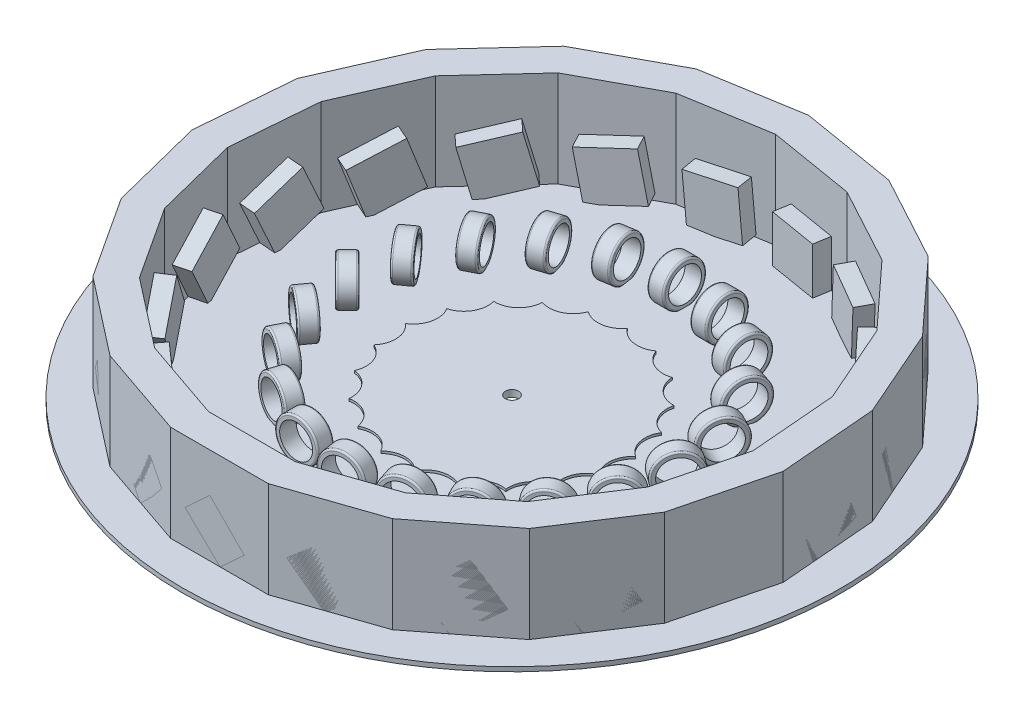
SolidWorks part; units mm, degrees
ref_plane "Front Plane" through (0, 0, 0) normal (0, 0, 1) x (1, 0, 0)
ref_plane "Top Plane" through (0, 0, 0) normal (0, 1, 0) x (1, 0, 0)
ref_plane "Right Plane" through (0, 0, 0) normal (1, 0, 0) x (0, 0, -1)
sketch "Sketch1" plane through (0, 0, 0) normal (0, 1, 0) x (1, 0, 0)
  circle A0 centre (0, 0) radius 100
  circle A1 centre (0, 0) radius 2
  dimension "D1" = 200
  dimension "D2" = 4
extrude "Base Platter" add sketch "Sketch1" along normal blind 0.75
sketch "Sketch2" plane through (0, 0.75, 0) normal (0, 1, 0) x (1, 0, 0)
  line L0 (0, 0) -> (0, 35) construction
  line L1 (0, 0) -> (10.3164, 33.445) construction
  line L2 (0, 0) -> (19.7162, 28.9184) construction
  line L3 (0, 0) -> (27.3641, 21.8221) construction
  line L4 (0, 0) -> (32.5806, 12.7869) construction
  line L5 (0, 0) -> (34.9021, 2.6156) construction
  line L6 (0, 0) -> (34.1225, -7.7882) construction
  line L7 (0, 0) -> (30.3109, -17.5) construction
  line L8 (0, 0) -> (23.806, -25.6568) construction
  line L9 (0, 0) -> (15.1859, -31.5339) construction
  line L10 (0, 0) -> (5.2165, -34.6091) construction
  line L11 (0, 0) -> (-5.2165, -34.6091) construction
  line L12 (0, 0) -> (-15.1859, -31.5339) construction
  line L13 (0, 0) -> (-23.806, -25.6568) construction
  line L14 (0, 0) -> (-30.3109, -17.5) construction
  line L15 (0, 0) -> (-34.1225, -7.7882) construction
  line L16 (0, 0) -> (-34.9021, 2.6156) construction
  line L17 (0, 0) -> (-32.5806, 12.7869) construction
  line L18 (0, 0) -> (-27.3641, 21.8221) construction
  line L19 (0, 0) -> (-19.7162, 28.9184) construction
  line L20 (0, 0) -> (-10.3164, 33.445) construction
  line L21 (0, 0) -> (4.4705, 29.665) construction
  line L22 (0, 0) -> (13.0158, 27.0294) construction
  line L23 (0, 0) -> (20.4046, 21.9921) construction
  line L24 (0, 0) -> (25.9804, 15.0006) construction
  line L25 (0, 0) -> (29.2477, 6.6764) construction
  line L26 (0, 0) -> (29.9162, -2.2412) construction
  line L27 (0, 0) -> (27.9265, -10.9595) construction
  line L28 (0, 0) -> (23.4554, -18.7041) construction
  line L29 (0, 0) -> (16.9002, -24.7867) construction
  line L30 (0, 0) -> (8.8434, -28.667) construction
  line L31 (0, 0) -> (0.0007, -30) construction
  line L32 (0, 0) -> (-8.8419, -28.6674) construction
  line L33 (0, 0) -> (-16.899, -24.7876) construction
  line L34 (0, 0) -> (-23.4545, -18.7053) construction
  line L35 (0, 0) -> (-27.9259, -10.9609) construction
  line L36 (0, 0) -> (-29.9161, -2.2426) construction
  line L37 (0, 0) -> (-29.248, 6.6749) construction
  line L38 (0, 0) -> (-25.9811, 14.9994) construction
  line L39 (0, 0) -> (-20.4057, 21.991) construction
  line L40 (0, 0) -> (-13.0172, 27.0287) construction
  line L41 (0, 0) -> (-4.472, 29.6648) construction
  circle A0 centre (0, 0) radius 30 construction
  circle A1 centre (0, 0) radius 2 construction
  circle A2 centre (0, 0) radius 35 construction
  arc A3 (-19.7162, 28.9184) -> (-10.3164, 33.445) centre (-17.2797, 35.8816) ccw
  arc A4 (-10.3164, 33.445) -> (0, 35) centre (-5.9357, 39.3807) ccw
  arc A5 (0, 35) -> (10.3164, 33.445) centre (5.9357, 39.3807) ccw
  arc A6 (10.3164, 33.445) -> (19.7162, 28.9184) centre (17.2797, 35.8816) ccw
  arc A7 (19.7162, 28.9184) -> (27.3641, 21.8221) centre (27.0883, 29.1942) ccw
  arc A8 (27.3641, 21.8221) -> (32.5806, 12.7869) centre (34.4899, 19.9128) ccw
  arc A9 (32.5806, 12.7869) -> (34.9021, 2.6156) centre (38.827, 8.862) ccw
  arc A10 (34.9021, 2.6156) -> (34.1225, -7.7882) centre (39.7142, -2.9762) ccw
  arc A11 (34.1225, -7.7882) -> (30.3109, -17.5) centre (37.0726, -14.5499) ccw
  arc A12 (30.3109, -17.5) -> (23.806, -25.6568) centre (31.1369, -24.8308) ccw
  arc A13 (23.806, -25.6568) -> (15.1859, -31.5339) centre (22.4345, -32.9054) ccw
  arc A14 (15.1859, -31.5339) -> (5.2165, -34.6091) centre (11.7388, -38.0562) ccw
  arc A15 (5.2165, -34.6091) -> (-5.2165, -34.6091) centre (0, -39.8256) ccw
  arc A16 (-5.2165, -34.6091) -> (-15.1859, -31.5339) centre (-11.7388, -38.0562) ccw
  arc A17 (-15.1859, -31.5339) -> (-23.806, -25.6568) centre (-22.4345, -32.9054) ccw
  arc A18 (-23.806, -25.6568) -> (-30.3109, -17.5) centre (-31.1369, -24.8308) ccw
  arc A19 (-30.3109, -17.5) -> (-34.1225, -7.7882) centre (-37.0726, -14.5499) ccw
  arc A20 (-34.1225, -7.7882) -> (-34.9021, 2.6156) centre (-39.7142, -2.9762) ccw
  arc A21 (-34.9021, 2.6156) -> (-32.5806, 12.7869) centre (-38.827, 8.862) ccw
  arc A22 (-32.5806, 12.7869) -> (-27.3641, 21.8221) centre (-34.4899, 19.9128) ccw
  arc A23 (-27.3641, 21.8221) -> (-19.7162, 28.9184) centre (-27.0883, 29.1942) ccw
  circle A24 centre (0, 0) radius 2
  point P28 (0, 0)
  point P50 (0, 0)
  point P112 (0, 0)
  dimension "D1" = 60
  dimension "D2" = 70
  dimension "D7" = 4
  dimension "D4" = 8.57
  dimension "D3" = 21
  dimension "D5" = 21
  dimension "D6" = 21
extrude "Inner Design" add sketch "Sketch2" along normal blind 1.3
sketch "Sketch3" plane through (0, 0.75, 0) normal (0, 1, 0) x (1, 0, 0)
  line L1 (0, 90) -> (-29.223, 85.1236)
  line L2 (-29.223, 85.1236) -> (-55.2791, 71.0226)
  line L3 (-55.2791, 71.0226) -> (-75.345, 49.2253)
  line L4 (-75.345, 49.2253) -> (-87.246, 22.0937)
  line L5 (-87.246, 22.0937) -> (-89.6926, -7.4321)
  line L6 (-89.6926, -7.4321) -> (-82.4196, -36.1526)
  line L7 (-82.4196, -36.1526) -> (-66.2152, -60.9553)
  line L8 (-66.2152, -60.9553) -> (-42.8353, -79.1526)
  line L9 (-42.8353, -79.1526) -> (-14.8135, -88.7725)
  line L10 (-14.8135, -88.7725) -> (14.8135, -88.7725)
  line L11 (14.8135, -88.7725) -> (42.8353, -79.1526)
  line L12 (42.8353, -79.1526) -> (66.2152, -60.9553)
  line L13 (66.2152, -60.9553) -> (82.4196, -36.1526)
  line L14 (82.4196, -36.1526) -> (89.6926, -7.4321)
  line L15 (89.6926, -7.4321) -> (87.246, 22.0937)
  line L16 (87.246, 22.0937) -> (75.345, 49.2253)
  line L17 (75.345, 49.2253) -> (55.2791, 71.0226)
  line L18 (55.2791, 71.0226) -> (29.223, 85.1236)
  line L19 (29.223, 85.1236) -> (0, 90)
  line L20 (0, 80) -> (-25.976, 75.6654)
  line L21 (-25.976, 75.6654) -> (-49.137, 63.1312)
  line L22 (-49.137, 63.1312) -> (-66.9733, 43.7559)
  line L23 (-66.9733, 43.7559) -> (-77.552, 19.6388)
  line L24 (-77.552, 19.6388) -> (-79.7268, -6.6063)
  line L25 (-79.7268, -6.6063) -> (-73.2619, -32.1356)
  line L26 (-73.2619, -32.1356) -> (-58.8579, -54.1825)
  line L27 (-58.8579, -54.1825) -> (-38.0758, -70.3579)
  line L28 (-38.0758, -70.3579) -> (-13.1676, -78.9089)
  line L29 (-13.1676, -78.9089) -> (13.1676, -78.9089)
  line L30 (13.1676, -78.9089) -> (38.0758, -70.3579)
  line L31 (38.0758, -70.3579) -> (58.8579, -54.1825)
  line L32 (58.8579, -54.1825) -> (73.2619, -32.1356)
  line L33 (73.2619, -32.1356) -> (79.7268, -6.6063)
  line L34 (79.7268, -6.6063) -> (77.552, 19.6388)
  line L35 (77.552, 19.6388) -> (66.9733, 43.7559)
  line L36 (66.9733, 43.7559) -> (49.137, 63.1312)
  line L37 (49.137, 63.1312) -> (25.976, 75.6654)
  line L38 (25.976, 75.6654) -> (0, 80)
  circle A0 centre (0, 0) radius 90 construction
  circle A1 centre (0, 0) radius 80 construction
  circle A2 centre (0, 0) radius 88.7725 construction
  circle A3 centre (0, 0) radius 78.9089 construction
  dimension "D1" = 180
  dimension "D2" = 160
extrude "Cube Face Reference" add sketch "Sketch3" along normal blind 29.8 separate body
sketch "Sketch4" plane through (14.6115, 0, -87.5618) normal (0.1646, 0, -0.9864) x (-0.9864, 0, -0.1646)
  line L0 (0, 0.75) -> (0, 30.55) construction
  line L1 (100, 0.75) -> (-100, 0.75) construction
  line L2 (-14.8135, 30.55) -> (14.8135, 30.55) construction
  line L3 (-14.8135, 0.75) -> (14.8135, 0.75) construction
  line L4 (-7.4075, 0.75) -> (7.4075, 0.75)
  line L5 (-7.4075, 0.75) -> (-7.4075, 15.57)
  line L6 (-7.4075, 15.57) -> (7.4075, 15.57)
  line L7 (7.4075, 0.75) -> (7.4075, 15.57)
  point P12 (0, 15.57)
  dimension "D1" = 14.815
  dimension "D2" = 14.82
extrude "First Cube" add sketch "Sketch4" against normal blind 14.82 separate body
sketch "Sketch5" plane through (42.251, 0, -78.0731) normal (0.4759, 0, -0.8795) x (-0.8795, 0, -0.4759)
  line L0 (-6.7728, 0.75) -> (7.9966, 1.9738)
  line L1 (-14.8135, 0.75) -> (14.8135, 0.75) construction
  line L2 (7.9966, 1.9738) -> (6.7728, 16.7432)
  line L3 (6.7728, 16.7432) -> (-7.9966, 15.5194)
  line L4 (-7.9966, 15.5194) -> (-6.7728, 0.75)
  line L5 (6.7728, 16.7432) -> (-6.7728, 0.75) construction
  line L6 (7.9966, 1.9738) -> (-7.9966, 15.5194) construction
  line L7 (100, 0.75) -> (-100, 0.75) construction
  line L8 (-14.8135, 30.55) -> (14.8135, 30.55) construction
  point P4 (0, 0)
  point P11 (0, 30.55)
  point P12 (0, 8.7466)
  dimension "D1" = 14.82
  dimension "D2" = 14.82
  dimension "D3" = 4.737
extrude "Boss-Extrude6" add sketch "Sketch5" against normal blind 14.82 separate body
sketch "Sketch6" plane through (65.3121, 0, -60.124) normal (0.7357, 0, -0.6773) x (-0.6773, 0, -0.7357)
  line L0 (-6.0893, 0.75) -> (-8.5286, 15.3679)
  line L1 (-14.8135, 0.75) -> (14.8135, 0.75) construction
  line L2 (-8.5286, 15.3679) -> (6.0893, 17.8072)
  line L3 (6.0893, 17.8072) -> (8.5286, 3.1893)
  line L4 (8.5286, 3.1893) -> (-6.0893, 0.75)
  line L5 (6.0893, 17.8072) -> (-6.0893, 0.75) construction
  line L6 (-8.5286, 15.3679) -> (8.5286, 3.1893) construction
  point P4 (0, 9.2786)
  dimension "D1" = 14.82
  dimension "D2" = 14.82
  dimension "D3" = 9.474
extrude "Boss-Extrude7" add sketch "Sketch6" against normal blind 14.82 separate body
sketch "Sketch7" plane through (81.2955, 0, -35.6595) normal (0.9158, 0, -0.4017) x (-0.4017, 0, -0.9158)
  line L0 (-5.3642, 0.75) -> (-9.0023, 15.1165)
  line L2 (-9.0023, 15.1165) -> (5.3642, 18.7546)
  line L3 (5.3642, 18.7546) -> (9.0023, 4.3881)
  line L4 (9.0023, 4.3881) -> (-5.3642, 0.75)
  line L5 (5.3642, 18.7546) -> (-5.3642, 0.75) construction
  line L6 (9.0023, 4.3881) -> (-9.0023, 15.1165) construction
  line L7 (100, 0.75) -> (-100, 0.75) construction
  line L8 (-14.8135, 0.75) -> (14.8135, 0.75) construction
  point P2 (0, 0)
  point P4 (0, 9.7523)
  dimension "D1" = 14.82
  dimension "D2" = 14.82
  dimension "D3" = 14.211
extrude "Boss-Extrude9" add sketch "Sketch7" against normal blind 14.82 separate body
sketch "Sketch8" plane through (88.4693, 0, -7.3308) normal (0.9966, 0, -0.0826) x (-0.0826, 0, -0.9966)
  line L0 (-4.6025, 0.75) -> (-9.4145, 14.767)
  line L2 (-9.4145, 14.767) -> (4.6025, 19.5791)
  line L3 (4.6025, 19.5791) -> (9.4145, 5.562)
  line L4 (9.4145, 5.562) -> (-4.6025, 0.75)
  line L5 (-14.8135, 0.75) -> (14.8135, 0.75) construction
  line L6 (-4.6025, 0.75) -> (4.6025, 19.5791) construction
  line L7 (9.4145, 5.562) -> (-9.4145, 14.767) construction
  line L8 (-14.8135, 30.55) -> (14.8135, 30.55) construction
  point P8 (0, 30.55)
  point P9 (0, 10.1645)
  dimension "D1" = 14.82
  dimension "D2" = 14.82
  dimension "D3" = 18.947
extrude "Boss-Extrude10" add sketch "Sketch8" against normal blind 14.82 separate body
sketch "Sketch9" plane through (86.0561, 0, 21.7924) normal (0.9694, 0, 0.2455) x (0.2455, 0, -0.9694)
  line L0 (-3.8093, 0.75) -> (-9.7624, 14.3218)
  line L1 (-14.8135, 0.75) -> (14.8135, 0.75) construction
  line L2 (-9.7624, 14.3218) -> (3.8093, 20.2749)
  line L3 (3.8093, 20.2749) -> (9.7624, 6.7031)
  line L4 (9.7624, 6.7031) -> (-3.8093, 0.75)
  line L5 (-3.8093, 0.75) -> (3.8093, 20.2749)
  line L6 (9.7624, 6.7031) -> (-9.7624, 14.3218)
  point P4 (0, 10.5124)
  dimension "D1" = 14.82
  dimension "D2" = 14.82
  dimension "D3" = 23.684
extrude "Boss-Extrude11" add sketch "Sketch9" against normal blind 14.82 separate body contours L6 L5 L2 | L6 L3 L5 | L4 L6 L5 | L5 L6 L0 region at (86.5432, 5.9885, 19.8687) region at (84.9455, 8.5281, 26.1779) region at (85.569, 15.0364, 23.716) region at (87.1667, 12.4968, 17.4069)
sketch "Sketch10" plane through (74.3174, 0, 48.554) normal (0.8372, 0, 0.5469) x (0.5469, 0, -0.8372)
  line L0 (-2.9901, 0.75) -> (-10.0437, 13.7838)
  line L1 (-14.8135, 0.75) -> (14.8135, 0.75) construction
  line L2 (-10.0437, 13.7838) -> (2.9901, 20.8373)
  line L3 (2.9901, 20.8373) -> (10.0437, 7.8035)
  line L4 (10.0437, 7.8035) -> (-2.9901, 0.75)
  line L5 (-2.9901, 0.75) -> (2.9901, 20.8373) construction
  line L6 (10.0437, 7.8035) -> (-10.0437, 13.7838) construction
  point P4 (0, 0.75)
  point P7 (0, 10.7937)
  dimension "D1" = 14.82
  dimension "D2" = 14.82
  dimension "D3" = 28.421
extrude "Boss-Extrude12" add sketch "Sketch10" against normal blind 14.82 separate body
sketch "Sketch11" plane through (54.5252, 0, 70.054) normal (0.6142, 0, 0.7891) x (0.7891, 0, -0.6142)
  line L0 (-2.1505, 0.75) -> (-10.2563, 13.1568)
  line L1 (-14.8135, 0.75) -> (14.8135, 0.75) construction
  line L2 (-10.2563, 13.1568) -> (2.1505, 21.2626)
  line L3 (2.1505, 21.2626) -> (10.2563, 8.8558)
  line L4 (10.2563, 8.8558) -> (-2.1505, 0.75)
  line L5 (2.1505, 21.2626) -> (-2.1505, 0.75) construction
  line L6 (10.2563, 8.8558) -> (-10.2563, 13.1568) construction
  line L7 (-14.8135, 30.55) -> (14.8135, 30.55) construction
  line L8 (100, 0.75) -> (-100, 0.75) construction
  point P8 (0, 30.55)
  point P9 (0, 11.0063)
  dimension "D1" = 14.82
  dimension "D2" = 14.82
  dimension "D3" = 33.158
extrude "Boss-Extrude14" add sketch "Sketch11" against normal blind 14.82 separate body
sketch "Sketch12" plane through (28.8244, 0, 83.9626) normal (0.3247, 0, 0.9458) x (0.9458, 0, -0.3247)
  line L0 (-1.2962, 0.75) -> (-10.3988, 12.4451)
  line L1 (100, 0.75) -> (-100, 0.75) construction
  line L2 (-10.3988, 12.4451) -> (1.2962, 21.5477)
  line L3 (1.2962, 21.5477) -> (10.3988, 9.8526)
  line L4 (10.3988, 9.8526) -> (-1.2962, 0.75)
  line L5 (1.2962, 21.5477) -> (-1.2962, 0.75) construction
  line L6 (-10.3988, 12.4451) -> (10.3988, 9.8526) construction
  line L7 (-14.8135, 30.55) -> (14.8135, 30.55) construction
  line L8 (-14.8135, 0.75) -> (14.8135, 0.75) construction
  point P8 (0, 30.55)
  point P9 (0, 11.1488)
  dimension "D1" = 14.82
  dimension "D2" = 14.82
  dimension "D3" = 37.895
extrude "Boss-Extrude15" add sketch "Sketch12" against normal blind 14.82 separate body
sketch "Sketch13" plane through (0, 0, 88.7725) normal (0, 0, 1) x (1, 0, 0)
  line L0 (-0.4331, 0.75) -> (-10.4704, 11.6534)
  line L1 (-14.8135, 0.75) -> (14.8135, 0.75) construction
  line L2 (-10.4704, 11.6534) -> (0.4331, 21.6907)
  line L3 (0.4331, 21.6907) -> (10.4704, 10.7873)
  line L4 (10.4704, 10.7873) -> (-0.4331, 0.75)
  line L5 (0.4331, 21.6907) -> (-0.4331, 0.75) construction
  line L6 (-10.4704, 11.6534) -> (10.4704, 10.7873) construction
  line L7 (100, 0.75) -> (-100, 0.75) construction
  point P8 (0, 0.75)
  point P9 (0, 11.2204)
  dimension "D1" = 14.82
  dimension "D2" = 14.82
  dimension "D3" = 42.632
extrude "Boss-Extrude16" add sketch "Sketch13" against normal blind 14.82 separate body
sketch "Sketch14" plane through (-28.8244, 0, 83.9626) normal (-0.3247, 0, 0.9458) x (0.9458, 0, 0.3247)
  line L0 (0.4331, 0.75) -> (-10.4704, 10.7873)
  line L1 (100, 0.75) -> (-100, 0.75) construction
  line L2 (-10.4704, 10.7873) -> (-0.4331, 21.6907)
  line L3 (-0.4331, 21.6907) -> (10.4704, 11.6534)
  line L4 (10.4704, 11.6534) -> (0.4331, 0.75)
  line L5 (0.4331, 0.75) -> (-0.4331, 21.6907) construction
  line L6 (-10.4704, 10.7873) -> (10.4704, 11.6534) construction
  line L7 (-14.8135, 0.75) -> (14.8135, 0.75) construction
  point P4 (0, 11.2204)
  dimension "D1" = 14.82
  dimension "D2" = 14.82
  dimension "D3" = 47.368
extrude "Boss-Extrude18" add sketch "Sketch14" against normal blind 14.82 separate body
sketch "Sketch15" plane through (-54.5252, 0, 70.054) normal (-0.6142, 0, 0.7891) x (0.7891, 0, 0.6142)
  line L0 (1.2962, 0.75) -> (-10.3988, 9.8526)
  line L1 (-14.8135, 0.75) -> (14.8135, 0.75) construction
  line L2 (-10.3988, 9.8526) -> (-1.2962, 21.5477)
  line L3 (-1.2962, 21.5477) -> (10.3988, 12.4451)
  line L4 (10.3988, 12.4451) -> (1.2962, 0.75)
  line L5 (1.2962, 0.75) -> (-1.2962, 21.5477) construction
  line L6 (10.3988, 12.4451) -> (-10.3988, 9.8526) construction
  line L7 (-14.8135, 30.55) -> (14.8135, 30.55) construction
  line L8 (100, 0.75) -> (-100, 0.75) construction
  point P8 (0, 30.55)
  point P9 (0, 11.1488)
  dimension "D1" = 14.82
  dimension "D2" = 14.82
  dimension "D3" = 52.105
extrude "Boss-Extrude19" add sketch "Sketch15" against normal blind 14.82 separate body
sketch "Sketch16" plane through (-74.3174, 0, 48.554) normal (-0.8372, 0, 0.5469) x (0.5469, 0, 0.8372)
  line L0 (2.1505, 0.75) -> (-10.2563, 8.8558)
  line L1 (-14.8135, 0.75) -> (14.8135, 0.75) construction
  line L2 (-10.2563, 8.8558) -> (-2.1505, 21.2626)
  line L3 (-2.1505, 21.2626) -> (10.2563, 13.1568)
  line L4 (10.2563, 13.1568) -> (2.1505, 0.75)
  line L5 (2.1505, 0.75) -> (-2.1505, 21.2626) construction
  line L6 (10.2563, 13.1568) -> (-10.2563, 8.8558) construction
  line L7 (-14.8135, 30.55) -> (14.8135, 30.55) construction
  point P8 (0, 30.55)
  point P9 (0, 11.0063)
  dimension "D1" = 14.82
  dimension "D2" = 14.82
  dimension "D3" = 56.842
extrude "Boss-Extrude20" add sketch "Sketch16" against normal blind 14.82 separate body
sketch "Sketch17" plane through (-86.0561, 0, 21.7924) normal (-0.9694, 0, 0.2455) x (0.2455, 0, 0.9694)
  line L0 (2.9901, 0.75) -> (-10.0437, 7.8035)
  line L1 (100, 0.75) -> (-100, 0.75) construction
  line L2 (-10.0437, 7.8035) -> (-2.9901, 20.8373)
  line L3 (-2.9901, 20.8373) -> (10.0437, 13.7838)
  line L4 (10.0437, 13.7838) -> (2.9901, 0.75)
  line L5 (2.9901, 0.75) -> (-2.9901, 20.8373) construction
  line L6 (10.0437, 13.7838) -> (-10.0437, 7.8035) construction
  line L7 (-14.8135, 30.55) -> (14.8135, 30.55) construction
  line L8 (-14.8135, 0.75) -> (14.8135, 0.75) construction
  point P8 (0, 30.55)
  point P9 (0, 10.7937)
  dimension "D1" = 14.82
  dimension "D2" = 14.82
  dimension "D3" = 14.82
  dimension "D4" = 61.579
extrude "Boss-Extrude21" add sketch "Sketch17" against normal blind 14.82 separate body
sketch "Sketch18" plane through (-88.4693, 0, -7.3308) normal (-0.9966, 0, -0.0826) x (-0.0826, 0, 0.9966)
  line L0 (3.8093, 0.75) -> (-9.7624, 6.7031)
  line L1 (100, 0.75) -> (-100, 0.75) construction
  line L2 (-9.7624, 6.7031) -> (-3.8093, 20.2749)
  line L3 (-3.8093, 20.2749) -> (9.7624, 14.3218)
  line L4 (9.7624, 14.3218) -> (3.8093, 0.75)
  line L5 (-3.8093, 20.2749) -> (3.8093, 0.75) construction
  line L6 (9.7624, 14.3218) -> (-9.7624, 6.7031) construction
  line L7 (-14.8135, 30.55) -> (14.8135, 30.55) construction
  line L8 (-14.8135, 0.75) -> (14.8135, 0.75) construction
  point P8 (0, 30.55)
  point P9 (0, 10.5124)
  dimension "D1" = 14.82
  dimension "D2" = 14.82
  dimension "D3" = 66.316
extrude "Boss-Extrude23" add sketch "Sketch18" against normal blind 14.82 separate body
sketch "Sketch19" plane through (-81.2955, 0, -35.6595) normal (-0.9158, 0, -0.4017) x (-0.4017, 0, 0.9158)
  line L0 (4.6025, 0.75) -> (-9.4145, 5.562)
  line L1 (-14.8135, 0.75) -> (14.8135, 0.75) construction
  line L2 (-9.4145, 5.562) -> (-4.6025, 19.5791)
  line L3 (-4.6025, 19.5791) -> (9.4145, 14.767)
  line L4 (9.4145, 14.767) -> (4.6025, 0.75)
  line L5 (4.6025, 0.75) -> (-4.6025, 19.5791) construction
  line L6 (9.4145, 14.767) -> (-9.4145, 5.562) construction
  line L7 (-14.8135, 30.55) -> (14.8135, 30.55) construction
  point P8 (0, 30.55)
  point P9 (0, 10.1645)
  dimension "D1" = 14.82
  dimension "D2" = 14.82
  dimension "D3" = 71.053
extrude "Boss-Extrude24" add sketch "Sketch19" against normal blind 14.82 separate body
sketch "Sketch20" plane through (-65.3121, 0, -60.124) normal (-0.7357, 0, -0.6773) x (-0.6773, 0, 0.7357)
  line L0 (5.3642, 0.75) -> (-9.0023, 4.3881)
  line L1 (100, 0.75) -> (-100, 0.75) construction
  line L2 (-9.0023, 4.3881) -> (-5.3642, 18.7546)
  line L3 (-5.3642, 18.7546) -> (9.0023, 15.1165)
  line L4 (9.0023, 15.1165) -> (5.3642, 0.75)
  line L5 (-5.3642, 18.7546) -> (5.3642, 0.75) construction
  line L6 (9.0023, 15.1165) -> (-9.0023, 4.3881) construction
  line L7 (-14.8135, 30.55) -> (14.8135, 30.55) construction
  point P8 (0, 30.55)
  point P9 (0, 9.7523)
  dimension "D1" = 14.82
  dimension "D2" = 14.82
  dimension "D3" = 75.789
extrude "Boss-Extrude25" add sketch "Sketch20" against normal blind 14.82 separate body
sketch "Sketch21" plane through (-42.251, 0, -78.0731) normal (-0.4759, 0, -0.8795) x (-0.8795, 0, 0.4759)
  line L0 (6.0893, 0.75) -> (-8.5286, 3.1893)
  line L1 (-14.8135, 0.75) -> (14.8135, 0.75) construction
  line L2 (-8.5286, 3.1893) -> (-6.0893, 17.8072)
  line L3 (-6.0893, 17.8072) -> (8.5286, 15.3679)
  line L4 (8.5286, 15.3679) -> (6.0893, 0.75)
  line L5 (6.0893, 0.75) -> (-6.0893, 17.8072) construction
  line L6 (8.5286, 15.3679) -> (-8.5286, 3.1893) construction
  line L7 (-14.8135, 30.55) -> (14.8135, 30.55) construction
  point P8 (0, 30.55)
  point P9 (0, 9.2786)
  dimension "D1" = 14.82
  dimension "D2" = 14.82
  dimension "D3" = 80.526
extrude "Boss-Extrude26" add sketch "Sketch21" against normal blind 14.82 separate body
sketch "Sketch22" plane through (-14.6115, 0, -87.5618) normal (-0.1646, 0, -0.9864) x (-0.9864, 0, 0.1646)
  line L0 (6.7728, 0.75) -> (-7.9966, 1.9738)
  line L1 (-14.8135, 0.75) -> (14.8135, 0.75) construction
  line L2 (-7.9966, 1.9738) -> (-6.7728, 16.7432)
  line L3 (-6.7728, 16.7432) -> (7.9966, 15.5194)
  line L4 (7.9966, 15.5194) -> (6.7728, 0.75)
  line L5 (6.7728, 0.75) -> (-6.7728, 16.7432) construction
  line L6 (-7.9966, 1.9738) -> (7.9966, 15.5194) construction
  line L7 (100, 0.75) -> (-100, 0.75) construction
  point P4 (0, 8.7466)
  dimension "D1" = 14.82
  dimension "D2" = 14.82
  dimension "D3" = 85.263
extrude "Boss-Extrude27" add sketch "Sketch22" against normal blind 14.82 separate body
sketch "Sketch23" plane through (0, 0.75, 0) normal (0, 1, 0) x (1, 0, 0)
  line L0 (0, 0) -> (0, 50) construction
  line L1 (0, 0) -> (15.4508, 47.5528) construction
  line L6 (0, 0) -> (29.3893, 40.4508) construction
  line L7 (0, 0) -> (40.4508, 29.3893) construction
  line L8 (0, 0) -> (47.5528, 15.4508) construction
  line L9 (0, 0) -> (50, 0) construction
  line L10 (0, 0) -> (47.5528, -15.4508) construction
  line L11 (0, 0) -> (40.4508, -29.3893) construction
  line L12 (0, 0) -> (29.3893, -40.4508) construction
  line L13 (0, 0) -> (15.4508, -47.5528) construction
  line L14 (0, 0) -> (0, -50) construction
  line L15 (0, 0) -> (-15.4508, -47.5528) construction
  line L16 (0, 0) -> (-29.3893, -40.4508) construction
  line L17 (0, 0) -> (-40.4508, -29.3893) construction
  line L18 (0, 0) -> (-47.5528, -15.4508) construction
  line L19 (0, 0) -> (-50, 0) construction
  line L20 (0, 0) -> (-47.5528, 15.4508) construction
  line L21 (0, 0) -> (-40.4508, 29.3893) construction
  line L22 (0, 0) -> (-29.3893, 40.4508) construction
  line L23 (0, 0) -> (-15.4508, 47.5528) construction
  line L24 (12.9508, 54.0528) -> (12.9508, 41.0528)
  line L25 (-2.5, 56.5) -> (2.5, 56.5)
  line L26 (-2.5, 56.5) -> (-2.5, 43.5)
  line L27 (-2.5, 43.5) -> (2.5, 43.5)
  line L28 (2.5, 56.5) -> (2.5, 43.5)
  line L29 (12.9508, 41.0528) -> (17.9508, 41.0528)
  line L30 (17.9508, 41.0528) -> (17.9508, 54.0528)
  line L31 (17.9508, 54.0528) -> (12.9508, 54.0528)
  line L32 (12.9508, 41.0528) -> (17.9508, 54.0528) construction
  line L33 (17.9508, 41.0528) -> (12.9508, 54.0528) construction
  line L34 (27.9369, 47.2619) -> (32.8753, 46.4797)
  line L35 (32.8753, 46.4797) -> (30.8417, 33.6398)
  line L36 (30.8417, 33.6398) -> (25.9032, 34.422)
  line L37 (25.9032, 34.422) -> (27.9369, 47.2619)
  line L38 (25.9032, 34.422) -> (32.8753, 46.4797) construction
  line L39 (30.8417, 33.6398) -> (27.9369, 47.2619) construction
  line L40 (40.0818, 36.3437) -> (36.0646, 23.9799)
  line L41 (36.0646, 23.9799) -> (40.8199, 22.4349)
  line L42 (40.8199, 22.4349) -> (44.8371, 34.7986)
  line L43 (44.8371, 34.7986) -> (40.0818, 36.3437)
  line L44 (40.8199, 22.4349) -> (40.0818, 36.3437) construction
  line L45 (44.8371, 34.7986) -> (36.0646, 23.9799) construction
  line L46 (48.2762, 22.3774) -> (42.3744, 10.7943)
  line L47 (42.3744, 10.7943) -> (46.8294, 8.5243)
  line L48 (46.8294, 8.5243) -> (52.7313, 20.1074)
  line L49 (52.7313, 20.1074) -> (48.2762, 22.3774)
  line L50 (46.8294, 8.5243) -> (48.2762, 22.3774) construction
  line L51 (52.7313, 20.1074) -> (42.3744, 10.7943) construction
  line L52 (51.7981, 6.7281) -> (44.1569, -3.7891)
  line L53 (44.1569, -3.7891) -> (48.2019, -6.7281)
  line L54 (48.2019, -6.7281) -> (55.8431, 3.7891)
  line L55 (55.8431, 3.7891) -> (51.7981, 6.7281)
  line L56 (48.2019, -6.7281) -> (51.7981, 6.7281) construction
  line L57 (55.8431, 3.7891) -> (44.1569, -3.7891) construction
  line L58 (50.3813, -9.0869) -> (41.1889, -18.2793)
  line L59 (41.1889, -18.2793) -> (44.7244, -21.8148)
  line L60 (44.7244, -21.8148) -> (53.9168, -12.6224)
  line L61 (53.9168, -12.6224) -> (50.3813, -9.0869)
  line L62 (44.7244, -21.8148) -> (50.3813, -9.0869) construction
  line L63 (53.9168, -12.6224) -> (41.1889, -18.2793) construction
  line L64 (44.24, -23.5461) -> (33.7228, -31.1873)
  line L65 (33.7228, -31.1873) -> (36.6617, -35.2324)
  line L66 (36.6617, -35.2324) -> (47.1789, -27.5912)
  line L67 (47.1789, -27.5912) -> (44.24, -23.5461)
  line L68 (36.6617, -35.2324) -> (44.24, -23.5461) construction
  line L69 (47.1789, -27.5912) -> (33.7228, -31.1873) construction
  line L70 (24.7327, -45.6293) -> (36.3158, -39.7274)
  line L71 (36.3158, -39.7274) -> (34.0458, -35.2724)
  line L72 (34.0458, -35.2724) -> (22.4627, -41.1743)
  line L73 (22.4627, -41.1743) -> (24.7327, -45.6293)
  line L74 (34.0458, -35.2724) -> (24.7327, -45.6293) construction
  line L75 (22.4627, -41.1743) -> (36.3158, -39.7274) construction
  line L76 (10.0415, -51.9391) -> (22.4053, -47.9219)
  line L77 (22.4053, -47.9219) -> (20.8602, -43.1666)
  line L78 (20.8602, -43.1666) -> (8.4964, -47.1838)
  line L79 (8.4964, -47.1838) -> (10.0415, -51.9391)
  line L80 (20.8602, -43.1666) -> (10.0415, -51.9391) construction
  line L81 (8.4964, -47.1838) -> (22.4053, -47.9219) construction
  line L82 (-6.0289, -53.486) -> (6.8111, -51.4524)
  line L83 (6.8111, -51.4524) -> (6.0289, -46.514)
  line L84 (6.0289, -46.514) -> (-6.8111, -48.5476)
  line L85 (-6.8111, -48.5476) -> (-6.0289, -53.486)
  line L86 (6.0289, -46.514) -> (-6.0289, -53.486) construction
  line L87 (-6.8111, -48.5476) -> (6.8111, -51.4524) construction
  line L88 (-21.9508, -50.0528) -> (-8.9508, -50.0528)
  line L89 (-8.9508, -50.0528) -> (-8.9508, -45.0528)
  line L90 (-8.9508, -45.0528) -> (-21.9508, -45.0528)
  line L91 (-21.9508, -45.0528) -> (-21.9508, -50.0528)
  line L92 (-8.9508, -45.0528) -> (-21.9508, -50.0528) construction
  line L93 (-21.9508, -45.0528) -> (-8.9508, -50.0528) construction
  line L94 (-36.3437, -40.8199) -> (-23.9799, -44.8371)
  line L95 (-23.9799, -44.8371) -> (-22.4349, -40.0818)
  line L96 (-22.4349, -40.0818) -> (-34.7986, -36.0646)
  line L97 (-34.7986, -36.0646) -> (-36.3437, -40.8199)
  line L98 (-22.4349, -40.0818) -> (-36.3437, -40.8199) construction
  line L99 (-34.7986, -36.0646) -> (-23.9799, -44.8371) construction
  line L100 (-47.3774, -28.6658) -> (-35.7943, -34.5677)
  line L101 (-35.7943, -34.5677) -> (-33.5243, -30.1127)
  line L102 (-33.5243, -30.1127) -> (-45.1074, -24.2108)
  line L103 (-45.1074, -24.2108) -> (-47.3774, -28.6658)
  line L104 (-33.5243, -30.1127) -> (-47.3774, -28.6658) construction
  line L105 (-45.1074, -24.2108) -> (-35.7943, -34.5677) construction
  line L106 (-54.2809, -13.6528) -> (-43.7637, -21.294)
  line L107 (-43.7637, -21.294) -> (-40.8248, -17.2489)
  line L108 (-40.8248, -17.2489) -> (-51.342, -9.6077)
  line L109 (-51.342, -9.6077) -> (-54.2809, -13.6528)
  line L110 (-40.8248, -17.2489) -> (-54.2809, -13.6528) construction
  line L111 (-51.342, -9.6077) -> (-43.7637, -21.294) construction
  line L112 (-56.364, 2.8284) -> (-47.1716, -6.364)
  line L113 (-47.1716, -6.364) -> (-43.636, -2.8284)
  line L114 (-43.636, -2.8284) -> (-52.8284, 6.364)
  line L115 (-52.8284, 6.364) -> (-56.364, 2.8284)
  line L116 (-43.636, -2.8284) -> (-56.364, 2.8284) construction
  line L117 (-52.8284, 6.364) -> (-47.1716, -6.364) construction
  line L118 (-53.396, 19.24) -> (-45.7548, 8.7228)
  line L119 (-45.7548, 8.7228) -> (-41.7097, 11.6617)
  line L120 (-41.7097, 11.6617) -> (-49.3509, 22.1789)
  line L121 (-49.3509, 22.1789) -> (-53.396, 19.24)
  line L122 (-41.7097, 11.6617) -> (-53.396, 19.24) construction
  line L123 (-49.3509, 22.1789) -> (-45.7548, 8.7228) construction
  line L124 (-45.6293, 34.0458) -> (-39.7274, 22.4627)
  line L125 (-39.7274, 22.4627) -> (-35.2724, 24.7327)
  line L126 (-35.2724, 24.7327) -> (-41.1743, 36.3158)
  line L127 (-41.1743, 36.3158) -> (-45.6293, 34.0458)
  line L128 (-35.2724, 24.7327) -> (-45.6293, 34.0458) construction
  line L129 (-41.1743, 36.3158) -> (-39.7274, 22.4627) construction
  line L130 (-33.7755, 45.8602) -> (-29.7583, 33.4964)
  line L131 (-29.7583, 33.4964) -> (-25.003, 35.0415)
  line L132 (-25.003, 35.0415) -> (-29.0202, 47.4053)
  line L133 (-29.0202, 47.4053) -> (-33.7755, 45.8602)
  line L134 (-25.003, 35.0415) -> (-33.7755, 45.8602) construction
  line L135 (-29.0202, 47.4053) -> (-29.7583, 33.4964) construction
  line L136 (-18.9369, 53.5817) -> (-16.9032, 40.7418)
  line L137 (-16.9032, 40.7418) -> (-11.9648, 41.5239)
  line L138 (-11.9648, 41.5239) -> (-13.9985, 54.3639)
  line L139 (-13.9985, 54.3639) -> (-18.9369, 53.5817)
  line L140 (-11.9648, 41.5239) -> (-18.9369, 53.5817) construction
  line L141 (-13.9985, 54.3639) -> (-16.9032, 40.7418) construction
  point P25 (0, 0)
  point P27 (0, 56.5)
  point P28 (2.5, 50)
  point P31 (15.4508, 47.5528)
  point P36 (29.3893, 40.4508)
  point P47 (-47.5528, -15.4508)
  point P50 (-50, 0)
  point P51 (-47.5528, 15.4508)
  point P54 (-40.4508, 29.3893)
  point P57 (-29.3893, 40.4508)
  point P60 (0, 0)
  point P63 (-15.4508, 47.5528)
  point P69 (29.3893, -40.4508)
  point P139 (0, 0)
  point P140 (40.4508, 29.3893)
  point P141 (47.5528, 15.4508)
  point P142 (50, 0)
  point P143 (57.2575, 7.0413)
  point P144 (47.5528, -15.4508)
  point P145 (57.2085, -13.843)
  point P146 (40.4508, -29.3893)
  point P147 (50.5627, -29.3893)
  point P148 (38.8762, -43.9505)
  point P149 (15.4508, -47.5528)
  point P150 (20.6773, -56.2093)
  point P151 (0, -50)
  point P152 (8.5265, -55.4359)
  point P153 (-15.4508, -47.5528)
  point P154 (-29.3893, -40.4508)
  point P155 (-40.4508, -29.3893)
  dimension "D1" = 50
  dimension "D2" = 20
  dimension "D3" = 5
  dimension "D4" = 13
  dimension "D5" = 5
  dimension "D6" = 13
  dimension "D7" = 18
  dimension "D8" = 5
  dimension "D9" = 13
  dimension "D10" = 27
  dimension "D11" = 5
  dimension "D12" = 13
  dimension "D13" = 36
  dimension "D14" = 5
  dimension "D15" = 13
  dimension "D16" = 45
  dimension "D17" = 5
  dimension "D18" = 13
  dimension "D19" = 54
  dimension "D20" = 5
  dimension "D21" = 13
  dimension "D22" = 63
  dimension "D23" = 5
  dimension "D24" = 13
  dimension "D25" = 72
  dimension "D26" = 5
  dimension "D27" = 13
  dimension "D28" = 81
  dimension "D29" = 5
  dimension "D30" = 13
  dimension "D31" = 90
  dimension "D32" = 5
  dimension "D33" = 13
  dimension "D34" = 99
  dimension "D35" = 5
  dimension "D36" = 13
  dimension "D37" = 108
  dimension "D38" = 5
  dimension "D39" = 13
  dimension "D40" = 108
  dimension "D41" = 5
  dimension "D42" = 13
  dimension "D43" = 117
  dimension "D44" = 5
  dimension "D45" = 13
  dimension "D46" = 126
  dimension "D47" = 5
  dimension "D48" = 13
  dimension "D49" = 135
  dimension "D50" = 5
  dimension "D51" = 13
  dimension "D52" = 144
  dimension "D53" = 5
  dimension "D54" = 13
  dimension "D55" = 153
  dimension "D56" = 5
  dimension "D57" = 13
  dimension "D58" = 162
  dimension "D59" = 5
  dimension "D60" = 13
  dimension "D61" = 171
extrude "Rings" add sketch "Sketch23" along normal blind 13 separate body
sketch "Sketch26" plane through (-5.2562, 0, 0.8325) normal (0.9877, 0, -0.1564) x (-0.1564, 0, -0.9877)
  line L0 (42.8844, 13.75) -> (55.8844, 13.75) construction
  line L1 (55.8844, 13.75) -> (55.8844, 0.75) construction
  line L3 (42.8844, 13.75) -> (55.8844, 13.75)
  line L4 (42.8844, 13.75) -> (42.8844, 0.75)
  line L5 (42.8844, 0.75) -> (55.8844, 0.75)
  line L6 (55.8844, 13.75) -> (55.8844, 0.75)
  circle A0 centre (49.3844, 7.25) radius 5
  circle A1 centre (49.3844, 7.25) radius 6.5
  point P5 (49.3844, 13.75)
  point P8 (55.8844, 7.25)
  line M2 (42.8844, 0.75) -> (55.8844, 0.75)
  line M3 (55.8844, 0.75) -> (55.8844, 13.75)
  line M4 (55.8844, 13.75) -> (42.8844, 13.75)
  line M5 (42.8844, 13.75) -> (42.8844, 0.75)
  dimension "D1" = 10
  dimension "D2" = 13
extrude "Cut-Extrude2" cut sketch "Sketch26" against normal up to surface (5 mm away) contours A0 | A1 L3 M5 | A1 L6 M4 | A1 L5 M3 | A1 L4 M2 region at (-12.1919, 12.2981, -42.958) region at (-13.7713, 12.2981, -52.9299) region at (-12.1919, 2.2019, -42.958) region at (-13.7713, 2.2019, -52.9299) region at (-12.9816, 7.25, -47.9439) up to face at (-17.9201, 7.25, -47.1617)
sketch "Sketch27" plane through (2.5, 0, 0) normal (1, 0, 0) x (0, 0, -1)
  line L0 (43.5, 13.75) -> (56.5, 13.75) construction
  line L1 (56.5, 13.75) -> (56.5, 0.75) construction
  line L3 (43.5, 13.75) -> (56.5, 13.75)
  line L4 (43.5, 13.75) -> (43.5, 0.75)
  line L5 (43.5, 0.75) -> (56.5, 0.75)
  line L6 (56.5, 13.75) -> (56.5, 0.75)
  circle A0 centre (50, 7.25) radius 5
  circle A1 centre (50, 7.25) radius 6.5
  point P4 (50, 13.75)
  point P7 (56.5, 7.25)
  line M2 (43.5, 0.75) -> (56.5, 0.75)
  line M3 (56.5, 0.75) -> (56.5, 13.75)
  line M4 (56.5, 13.75) -> (43.5, 13.75)
  line M5 (43.5, 13.75) -> (43.5, 0.75)
  dimension "D1" = 10
  dimension "D2" = 13
extrude "Cut-Extrude3" cut sketch "Sketch27" against normal up to surface (5 mm away) contours A0 | A1 L3 M5 | A1 L4 M2 | A1 L6 M4 | A1 L5 M3 region at (2.5, 12.2981, -44.9519) region at (2.5, 12.2981, -55.0481) region at (2.5, 2.2019, -44.9519) region at (2.5, 2.2019, -55.0481) region at (2.5, 7.25, -50) up to face at (-2.5, 7.25, -50)
sketch "Sketch28" plane through (17.9508, 0, 0) normal (1, 0, 0) x (0, 0, -1)
  line L0 (41.0528, 13.75) -> (54.0528, 13.75) construction
  line L1 (54.0528, 13.75) -> (54.0528, 0.75) construction
  line L3 (41.0528, 13.75) -> (54.0528, 13.75)
  line L4 (41.0528, 13.75) -> (41.0528, 0.75)
  line L5 (41.0528, 0.75) -> (54.0528, 0.75)
  line L6 (54.0528, 13.75) -> (54.0528, 0.75)
  circle A0 centre (47.5528, 7.25) radius 5
  circle A1 centre (47.5528, 7.25) radius 6.5
  point P4 (47.5528, 13.75)
  point P7 (54.0528, 7.25)
  line M2 (41.0528, 0.75) -> (54.0528, 0.75)
  line M3 (54.0528, 0.75) -> (54.0528, 13.75)
  line M4 (54.0528, 13.75) -> (41.0528, 13.75)
  line M5 (41.0528, 13.75) -> (41.0528, 0.75)
  dimension "D1" = 10
  dimension "D2" = 13
extrude "Cut-Extrude4" cut sketch "Sketch28" against normal up to surface (5 mm away) contours A1 L3 M5 | A1 L4 M2 | A0 | A1 L6 M4 | A1 L5 M3 region at (17.9508, 12.2981, -42.5047) region at (17.9508, 12.2981, -52.6009) region at (17.9508, 2.2019, -42.5047) region at (17.9508, 2.2019, -52.6009) region at (17.9508, 7.25, -47.5528) up to face at (12.9508, 7.25, -47.5528)
sketch "Sketch29" plane through (24.8893, 0, 3.9421) normal (0.9877, 0, 0.1564) x (0.1564, 0, -0.9877)
  line L0 (38.0503, 13.75) -> (51.0503, 13.75) construction
  line L1 (51.0503, 13.75) -> (51.0503, 0.75) construction
  line L3 (38.0503, 13.75) -> (51.0503, 13.75)
  line L4 (38.0503, 13.75) -> (38.0503, 0.75)
  line L5 (38.0503, 0.75) -> (51.0503, 0.75)
  line L6 (51.0503, 13.75) -> (51.0503, 0.75)
  circle A0 centre (44.5503, 7.25) radius 5
  circle A1 centre (44.5503, 7.25) radius 6.5
  point P4 (44.5503, 13.75)
  point P7 (51.0503, 7.25)
  line M2 (38.0503, 0.75) -> (51.0503, 0.75)
  line M3 (51.0503, 0.75) -> (51.0503, 13.75)
  line M4 (51.0503, 13.75) -> (38.0503, 13.75)
  line M5 (38.0503, 13.75) -> (38.0503, 0.75)
  dimension "D1" = 10
  dimension "D2" = 13
extrude "Cut-Extrude5" cut sketch "Sketch29" against normal up to surface (5 mm away) contours A0 | A1 L3 M5 | A1 L4 M2 | A1 L5 M3 | A1 L6 M4 region at (31.0688, 12.2981, -35.0738) region at (32.6482, 12.2981, -45.0457) region at (31.0688, 2.2019, -35.0738) region at (32.6482, 2.2019, -45.0457) region at (31.8585, 7.25, -40.0598) up to face at (26.92, 7.25, -40.8419)
sketch "Sketch30" plane through (30.3285, 0, 9.8543) normal (0.9511, 0, 0.309) x (0.309, 0, -0.9511)
  line L0 (33.9508, 13.75) -> (46.9508, 13.75) construction
  line L1 (46.9508, 13.75) -> (46.9508, 0.75) construction
  line L3 (33.9508, 13.75) -> (46.9508, 13.75)
  line L4 (33.9508, 13.75) -> (33.9508, 0.75)
  line L5 (33.9508, 0.75) -> (46.9508, 0.75)
  line L6 (46.9508, 13.75) -> (46.9508, 0.75)
  circle A0 centre (40.4508, 7.25) radius 5
  circle A1 centre (40.4508, 7.25) radius 6.5
  point P4 (40.4508, 13.75)
  point P7 (46.9508, 7.25)
  line M2 (33.9508, 0.75) -> (46.9508, 0.75)
  line M3 (46.9508, 0.75) -> (46.9508, 13.75)
  line M4 (46.9508, 13.75) -> (33.9508, 13.75)
  line M5 (33.9508, 13.75) -> (33.9508, 0.75)
  dimension "D1" = 10
  dimension "D2" = 13
extrude "Cut-Extrude6" cut sketch "Sketch30" against normal up to surface (5 mm away) contours A1 L3 M5 | A1 L4 M2 | A0 | A1 L6 M4 | A1 L5 M3 region at (41.2685, 12.2981, -23.8157) region at (44.3884, 12.2981, -33.4178) region at (41.2685, 2.2019, -23.8157) region at (44.3884, 2.2019, -33.4178) region at (42.8285, 7.25, -28.6167) up to face at (38.0732, 7.25, -30.1618)
sketch "Sketch31" plane through (33.7294, 0, 17.186) normal (0.891, 0, 0.454) x (0.454, 0, -0.891)
  line L0 (28.8553, 13.75) -> (41.8553, 13.75) construction
  line L1 (41.8553, 13.75) -> (41.8553, 0.75) construction
  line L3 (28.8553, 13.75) -> (41.8553, 13.75)
  line L4 (28.8553, 13.75) -> (28.8553, 0.75)
  line L5 (28.8553, 0.75) -> (41.8553, 0.75)
  line L6 (41.8553, 13.75) -> (41.8553, 0.75)
  circle A0 centre (35.3553, 7.25) radius 5
  circle A1 centre (35.3553, 7.25) radius 6.5
  point P4 (35.3553, 13.75)
  point P7 (41.8553, 7.25)
  line M2 (28.8553, 0.75) -> (41.8553, 0.75)
  line M3 (41.8553, 0.75) -> (41.8553, 13.75)
  line M4 (41.8553, 13.75) -> (28.8553, 13.75)
  line M5 (28.8553, 13.75) -> (28.8553, 0.75)
  dimension "D1" = 10
  dimension "D2" = 13
extrude "Cut-Extrude7" cut sketch "Sketch31" against normal up to surface (5 mm away) contours A1 L3 M5 | A1 L4 M2 | A0 | A1 L6 M4 | A1 L5 M3 region at (47.4885, 12.2981, -9.818) region at (52.0721, 12.2981, -18.8138) region at (47.4885, 2.2019, -9.818) region at (52.0721, 2.2019, -18.8138) region at (49.7803, 7.25, -14.3159) up to face at (45.3253, 7.25, -16.5858)
sketch "Sketch32" plane through (34.748, 0, 25.2459) normal (0.809, 0, 0.5878) x (0.5878, 0, -0.809)
  line L0 (22.8893, 13.75) -> (35.8893, 13.75) construction
  line L1 (35.8893, 13.75) -> (35.8893, 0.75) construction
  line L3 (22.8893, 13.75) -> (35.8893, 13.75)
  line L4 (22.8893, 13.75) -> (22.8893, 0.75)
  line L5 (22.8893, 0.75) -> (35.8893, 0.75)
  line L6 (35.8893, 13.75) -> (35.8893, 0.75)
  circle A0 centre (29.3893, 7.25) radius 5
  circle A1 centre (29.3893, 7.25) radius 6.5
  point P5 (29.3893, 13.75)
  point P8 (35.8893, 7.25)
  line M2 (22.8893, 0.75) -> (35.8893, 0.75)
  line M3 (35.8893, 0.75) -> (35.8893, 13.75)
  line M4 (35.8893, 13.75) -> (22.8893, 13.75)
  line M5 (22.8893, 13.75) -> (22.8893, 0.75)
  dimension "D1" = 10
  dimension "D2" = 13
extrude "Cut-Extrude8" cut sketch "Sketch32" against normal up to surface (5 mm away) contours A1 L3 M5 | A1 L4 M2 | A0 | A1 L6 M4 | A1 L5 M3 region at (49.0553, 12.2981, 5.5535) region at (54.9897, 12.2981, -2.6145) region at (49.0553, 2.2019, 5.5535) region at (54.9897, 2.2019, -2.6145) region at (52.0225, 7.25, 1.4695) up to face at (47.9775, 7.25, -1.4695)
sketch "Sketch33" plane through (33.2696, 0, 33.2696) normal (0.7071, 0, 0.7071) x (0.7071, 0, -0.7071)
  line L0 (16.1995, 13.75) -> (29.1995, 13.75) construction
  line L1 (29.1995, 13.75) -> (29.1995, 0.75) construction
  line L3 (16.1995, 13.75) -> (29.1995, 13.75)
  line L4 (16.1995, 13.75) -> (16.1995, 0.75)
  line L5 (16.1995, 0.75) -> (29.1995, 0.75)
  line L6 (29.1995, 13.75) -> (29.1995, 0.75)
  circle A0 centre (22.6995, 7.25) radius 5
  circle A1 centre (22.6995, 7.25) radius 6.5
  point P4 (22.6995, 13.75)
  point P7 (29.1995, 7.25)
  line M2 (16.1995, 0.75) -> (29.1995, 0.75)
  line M3 (29.1995, 0.75) -> (29.1995, 13.75)
  line M4 (29.1995, 13.75) -> (16.1995, 13.75)
  line M5 (16.1995, 13.75) -> (16.1995, 0.75)
  dimension "D1" = 10
  dimension "D2" = 13
extrude "Cut-Extrude9" cut sketch "Sketch33" against normal up to surface (5 mm away) contours A1 L3 M5 | A1 L4 M2 | A0 | A1 L6 M4 | A1 L5 M3 region at (45.751, 12.2981, 20.7882) region at (52.8901, 12.2981, 13.6491) region at (45.751, 2.2019, 20.7882) region at (52.8901, 2.2019, 13.6491) region at (49.3206, 7.25, 17.2186) up to face at (45.7851, 7.25, 13.6831)
sketch "Sketch34" plane through (29.4203, 0, 40.4936) normal (0.5878, 0, 0.809) x (0.809, 0, -0.5878)
  line L0 (8.9508, 13.75) -> (21.9508, 13.75) construction
  line L1 (21.9508, 13.75) -> (21.9508, 0.75) construction
  line L3 (8.9508, 13.75) -> (21.9508, 13.75)
  line L4 (8.9508, 13.75) -> (8.9508, 0.75)
  line L5 (8.9508, 0.75) -> (21.9508, 0.75)
  line L6 (21.9508, 13.75) -> (21.9508, 0.75)
  circle A0 centre (15.4508, 7.25) radius 5
  circle A1 centre (15.4508, 7.25) radius 6.5
  point P4 (15.4508, 13.75)
  point P7 (21.9508, 7.25)
  line M2 (8.9508, 0.75) -> (21.9508, 0.75)
  line M3 (21.9508, 0.75) -> (21.9508, 13.75)
  line M4 (21.9508, 13.75) -> (8.9508, 13.75)
  line M5 (8.9508, 13.75) -> (8.9508, 0.75)
  dimension "D1" = 10
  dimension "D2" = 13
extrude "Cut-Extrude10" cut sketch "Sketch34" against normal up to surface (5 mm away) contours A1 L4 M2 | A1 L3 M5 | A0 | A1 L6 M4 | A1 L5 M3 region at (37.8363, 12.2981, 34.379) region at (46.0043, 12.2981, 28.4446) region at (37.8363, 2.2019, 34.379) region at (46.0043, 2.2019, 28.4446) region at (41.9203, 7.25, 31.4118) up to face at (38.9814, 7.25, 27.3667)
sketch "Sketch35" plane through (23.555, 0, 46.2294) normal (0.454, 0, 0.891) x (0.891, 0, -0.454)
  line L0 (1.3217, 13.75) -> (14.3217, 13.75) construction
  line L1 (14.3217, 13.75) -> (14.3217, 0.75) construction
  line L3 (1.3217, 13.75) -> (14.3217, 13.75)
  line L4 (1.3217, 13.75) -> (1.3217, 0.75)
  line L5 (1.3217, 0.75) -> (14.3217, 0.75)
  line L6 (14.3217, 13.75) -> (14.3217, 0.75)
  circle A0 centre (7.8217, 7.25) radius 5
  circle A1 centre (7.8217, 7.25) radius 6.5
  point P4 (7.8217, 13.75)
  point P7 (14.3217, 7.25)
  line M2 (1.3217, 0.75) -> (14.3217, 0.75)
  line M3 (14.3217, 0.75) -> (14.3217, 13.75)
  line M4 (14.3217, 13.75) -> (1.3217, 13.75)
  line M5 (1.3217, 13.75) -> (1.3217, 0.75)
  dimension "D1" = 10
  dimension "D2" = 13
extrude "Cut-Extrude11" cut sketch "Sketch35" against normal up to surface (5 mm away) contours A1 L4 M2 | A1 L3 M5 | A0 | A1 L6 M4 | A1 L5 M3 region at (26.0263, 12.2981, 44.9702) region at (35.0221, 12.2981, 40.3866) region at (26.0263, 2.2019, 44.9702) region at (35.0221, 2.2019, 40.3866) region at (30.5242, 7.25, 42.6784) up to face at (28.2543, 7.25, 38.2233)
sketch "Sketch36" plane through (16.2234, 0, 49.9305) normal (0.309, 0, 0.9511) x (0.9511, 0, -0.309)
  line L0 (-6.5, 13.75) -> (6.5, 13.75) construction
  line L1 (6.5, 13.75) -> (6.5, 0.75) construction
  line L3 (-6.5, 13.75) -> (6.5, 13.75)
  line L4 (-6.5, 13.75) -> (-6.5, 0.75)
  line L5 (-6.5, 0.75) -> (6.5, 0.75)
  line L6 (6.5, 13.75) -> (6.5, 0.75)
  circle A0 centre (0, 7.25) radius 5
  circle A1 centre (0, 7.25) radius 6.5
  point P4 (0, 13.75)
  point P7 (6.5, 7.25)
  line M2 (-6.5, 0.75) -> (6.5, 0.75)
  line M3 (6.5, 0.75) -> (6.5, 13.75)
  line M4 (6.5, 13.75) -> (-6.5, 13.75)
  line M5 (-6.5, 13.75) -> (-6.5, 0.75)
  dimension "D1" = 10
  dimension "D2" = 13
extrude "Cut-Extrude12" cut sketch "Sketch36" against normal up to surface (5 mm away) contours A1 L3 M5 | A1 L4 M2 | A0 | A1 L5 M3 | A1 L6 M4 region at (11.4224, 12.2981, 51.4904) region at (21.0244, 12.2981, 48.3705) region at (11.4224, 2.2019, 51.4904) region at (21.0244, 2.2019, 48.3705) region at (16.2234, 7.25, 49.9305) up to face at (14.6783, 7.25, 45.1752)
sketch "Sketch37" plane through (8.1165, 0, 51.2456) normal (0.1564, 0, 0.9877) x (0.9877, 0, -0.1564)
  line L0 (-14.3217, 13.75) -> (-1.3217, 13.75) construction
  line L1 (-1.3217, 13.75) -> (-1.3217, 0.75) construction
  line L3 (-1.3217, 0.75) -> (-14.3217, 0.75)
  line L4 (-1.3217, 0.75) -> (-1.3217, 13.75)
  line L5 (-1.3217, 13.75) -> (-14.3217, 13.75)
  line L6 (-14.3217, 0.75) -> (-14.3217, 13.75)
  circle A0 centre (-7.8217, 7.25) radius 5
  circle A1 centre (-7.8217, 7.25) radius 6.5
  point P4 (-7.8217, 13.75)
  point P7 (-1.3217, 7.25)
  line M2 (-14.3217, 0.75) -> (-1.3217, 0.75)
  line M3 (-1.3217, 0.75) -> (-1.3217, 13.75)
  line M4 (-1.3217, 13.75) -> (-14.3217, 13.75)
  line M5 (-14.3217, 13.75) -> (-14.3217, 0.75)
  dimension "D1" = 10
  dimension "D2" = 13
extrude "Cut-Extrude13" cut sketch "Sketch37" against normal up to surface (5 mm away) contours A1 L5 M5 | A1 L6 M2 | A0 | A1 L4 M4 | A1 L3 M3 region at (5.377, 2.2019, 51.6795) region at (-4.5949, 2.2019, 53.2589) region at (5.377, 12.2981, 51.6795) region at (-4.5949, 12.2981, 53.2589) region at (0.3911, 7.25, 52.4692) up to face at (-0.3911, 7.25, 47.5308)
sketch "Sketch38" plane through (0, 0, 50.0528) normal (0, 0, 1) x (1, 0, 0)
  line L0 (-21.9508, 13.75) -> (-8.9508, 13.75) construction
  line L1 (-8.9508, 13.75) -> (-8.9508, 0.75) construction
  line L3 (-21.9508, 13.75) -> (-8.9508, 13.75)
  line L4 (-21.9508, 13.75) -> (-21.9508, 0.75)
  line L5 (-21.9508, 0.75) -> (-8.9508, 0.75)
  line L6 (-8.9508, 13.75) -> (-8.9508, 0.75)
  circle A0 centre (-15.4508, 7.25) radius 5
  circle A1 centre (-15.4508, 7.25) radius 6.5
  point P4 (-15.4508, 13.75)
  point P7 (-8.9508, 7.25)
  line M2 (-21.9508, 0.75) -> (-8.9508, 0.75)
  line M3 (-8.9508, 0.75) -> (-8.9508, 13.75)
  line M4 (-8.9508, 13.75) -> (-21.9508, 13.75)
  line M5 (-21.9508, 13.75) -> (-21.9508, 0.75)
  dimension "D1" = 10
  dimension "D2" = 13
extrude "Cut-Extrude14" cut sketch "Sketch38" against normal up to surface (5 mm away) contours A1 L3 M5 | A1 L4 M2 | A0 | A1 L6 M4 | A1 L5 M3 region at (-20.499, 12.2981, 50.0528) region at (-10.4027, 12.2981, 50.0528) region at (-20.499, 2.2019, 50.0528) region at (-10.4027, 2.2019, 50.0528) region at (-15.4508, 7.25, 50.0528) up to face at (-15.4508, 7.25, 45.0528)
sketch "Sketch39" plane through (-15.4672, 0, 47.6031) normal (-0.309, 0, 0.9511) x (0.9511, 0, 0.309)
  line L0 (-21.9508, 13.75) -> (-8.9508, 13.75) construction
  line L1 (-8.9508, 13.75) -> (-8.9508, 0.75) construction
  line L3 (-21.9508, 13.75) -> (-8.9508, 13.75)
  line L4 (-21.9508, 13.75) -> (-21.9508, 0.75)
  line L5 (-21.9508, 0.75) -> (-8.9508, 0.75)
  line L6 (-8.9508, 13.75) -> (-8.9508, 0.75)
  circle A0 centre (-15.4508, 7.25) radius 5
  circle A1 centre (-15.4508, 7.25) radius 6.5
  point P4 (-15.4508, 13.75)
  point P7 (-8.9508, 7.25)
  line M2 (-21.9508, 0.75) -> (-8.9508, 0.75)
  line M3 (-8.9508, 0.75) -> (-8.9508, 13.75)
  line M4 (-8.9508, 13.75) -> (-21.9508, 13.75)
  line M5 (-21.9508, 13.75) -> (-21.9508, 0.75)
  dimension "D1" = 10
  dimension "D2" = 13
extrude "Cut-Extrude15" cut sketch "Sketch39" against normal up to surface (5 mm away) contours A1 L3 M5 | A1 L4 M2 | A1 L6 M4 | A0 | A1 L5 M3 region at (-34.9628, 12.2981, 41.2685) region at (-25.3608, 12.2981, 44.3884) region at (-34.9628, 2.2019, 41.2685) region at (-25.3608, 2.2019, 44.3884) region at (-30.1618, 7.25, 42.8285) up to face at (-28.6167, 7.25, 38.0732)
sketch "Sketch40" plane through (-21.3604, 0, 41.9221) normal (-0.454, 0, 0.891) x (0.891, 0, 0.454)
  line L0 (-29.1995, 13.75) -> (-16.1995, 13.75) construction
  line L1 (-16.1995, 13.75) -> (-16.1995, 0.75) construction
  line L3 (-29.1995, 13.75) -> (-16.1995, 13.75)
  line L4 (-29.1995, 13.75) -> (-29.1995, 0.75)
  line L5 (-29.1995, 0.75) -> (-16.1995, 0.75)
  line L6 (-16.1995, 13.75) -> (-16.1995, 0.75)
  circle A0 centre (-22.6995, 7.25) radius 5
  circle A1 centre (-22.6995, 7.25) radius 6.5
  point P4 (-22.6995, 13.75)
  point P7 (-16.1995, 7.25)
  line M2 (-29.1995, 0.75) -> (-16.1995, 0.75)
  line M3 (-16.1995, 0.75) -> (-16.1995, 13.75)
  line M4 (-16.1995, 13.75) -> (-29.1995, 13.75)
  line M5 (-29.1995, 13.75) -> (-29.1995, 0.75)
  dimension "D1" = 10
  dimension "D2" = 13
extrude "Cut-Extrude16" cut sketch "Sketch40" against normal up to surface (5 mm away) contours A1 L3 M5 | A1 L6 M4 | A0 | A1 L5 M3 | A1 L4 M2 region at (-46.0837, 12.2981, 29.325) region at (-37.0879, 12.2981, 33.9086) region at (-46.0837, 2.2019, 29.325) region at (-37.0879, 2.2019, 33.9086) region at (-41.5858, 7.25, 31.6168) up to face at (-39.3159, 7.25, 27.1617)
sketch "Sketch41" plane through (-25.2459, 0, 34.748) normal (-0.5878, 0, 0.809) x (0.809, 0, 0.5878)
  line L0 (-35.8893, 13.75) -> (-22.8893, 13.75) construction
  line L1 (-35.8893, 13.75) -> (-35.8893, 0.75) construction
  line L3 (-35.8893, 13.75) -> (-22.8893, 13.75)
  line L4 (-35.8893, 13.75) -> (-35.8893, 0.75)
  line L5 (-35.8893, 0.75) -> (-22.8893, 0.75)
  line L6 (-22.8893, 13.75) -> (-22.8893, 0.75)
  circle A0 centre (-29.3893, 7.25) radius 5
  circle A1 centre (-29.3893, 7.25) radius 6.5
  point P4 (-29.3893, 13.75)
  point P7 (-35.8893, 7.25)
  line M2 (-35.8893, 0.75) -> (-22.8893, 0.75)
  line M3 (-22.8893, 0.75) -> (-22.8893, 13.75)
  line M4 (-22.8893, 13.75) -> (-35.8893, 13.75)
  line M5 (-35.8893, 13.75) -> (-35.8893, 0.75)
  dimension "D1" = 10
  dimension "D2" = 13
extrude "Cut-Extrude17" cut sketch "Sketch41" against normal up to surface (5 mm away) contours A1 L6 M4 | A1 L3 M5 | A0 | A1 L5 M3 | A1 L4 M2 region at (-53.1063, 12.2981, 14.5062) region at (-44.9383, 12.2981, 20.4406) region at (-53.1063, 2.2019, 14.5062) region at (-44.9383, 2.2019, 20.4406) region at (-49.0223, 7.25, 17.4734) up to face at (-46.0834, 7.25, 13.4283)
sketch "Sketch42" plane through (-26.7678, 0, 26.7678) normal (-0.7071, 0, 0.7071) x (0.7071, 0, 0.7071)
  line L0 (-41.8553, 13.75) -> (-28.8553, 13.75) construction
  line L1 (-28.8553, 13.75) -> (-28.8553, 0.75) construction
  line L3 (-41.8553, 13.75) -> (-28.8553, 13.75)
  line L4 (-41.8553, 13.75) -> (-41.8553, 0.75)
  line L5 (-41.8553, 0.75) -> (-28.8553, 0.75)
  line L6 (-28.8553, 13.75) -> (-28.8553, 0.75)
  circle A0 centre (-35.3553, 7.25) radius 5
  circle A1 centre (-35.3553, 7.25) radius 6.5
  point P4 (-35.3553, 13.75)
  point P7 (-28.8553, 7.25)
  line M2 (-41.8553, 0.75) -> (-28.8553, 0.75)
  line M3 (-28.8553, 0.75) -> (-28.8553, 13.75)
  line M4 (-28.8553, 13.75) -> (-41.8553, 13.75)
  line M5 (-41.8553, 13.75) -> (-41.8553, 0.75)
  dimension "D1" = 10
  dimension "D2" = 13
extrude "Cut-Extrude18" cut sketch "Sketch42" against normal up to surface (5 mm away) contours A1 L3 M5 | A1 L6 M4 | A0 | A1 L5 M3 | A1 L4 M2 region at (-55.3373, 12.2981, -1.8018) region at (-48.1982, 12.2981, 5.3373) region at (-55.3373, 2.2019, -1.8018) region at (-48.1982, 2.2019, 5.3373) region at (-51.7678, 7.25, 1.7678) up to face at (-48.2322, 7.25, -1.7678)
sketch "Sketch43" plane through (-25.799, 0, 18.744) normal (-0.809, 0, 0.5878) x (0.5878, 0, 0.809)
  line L0 (-46.9508, 13.75) -> (-33.9508, 13.75) construction
  line L1 (-46.9508, 13.75) -> (-46.9508, 0.75) construction
  line L3 (-46.9508, 13.75) -> (-33.9508, 13.75)
  line L4 (-46.9508, 13.75) -> (-46.9508, 0.75)
  line L5 (-46.9508, 0.75) -> (-33.9508, 0.75)
  line L6 (-33.9508, 13.75) -> (-33.9508, 0.75)
  circle A0 centre (-40.4508, 7.25) radius 5
  circle A1 centre (-40.4508, 7.25) radius 6.5
  point P4 (-40.4508, 13.75)
  point P7 (-46.9508, 7.25)
  line M2 (-46.9508, 0.75) -> (-33.9508, 0.75)
  line M3 (-33.9508, 0.75) -> (-33.9508, 13.75)
  line M4 (-33.9508, 13.75) -> (-46.9508, 13.75)
  line M5 (-46.9508, 13.75) -> (-46.9508, 0.75)
  dimension "D1" = 10
  dimension "D2" = 13
extrude "Cut-Extrude19" cut sketch "Sketch43" against normal up to surface (5 mm away) contours A1 L5 M3 | A1 L6 M4 | A0 | A1 L3 M5 | A1 L4 M2 region at (-52.5426, 12.2981, -18.0654) region at (-46.6082, 12.2981, -9.8974) region at (-52.5426, 2.2019, -18.0654) region at (-46.6082, 2.2019, -9.8974) region at (-49.5754, 7.25, -13.9814) up to face at (-45.5303, 7.25, -16.9203)
sketch "Sketch44" plane through (-22.4529, 0, 11.4403) normal (-0.891, 0, 0.454) x (0.454, 0, 0.891)
  line L0 (-51.0503, 13.75) -> (-38.0503, 13.75) construction
  line L1 (-51.0503, 13.75) -> (-51.0503, 0.75) construction
  line L3 (-51.0503, 13.75) -> (-38.0503, 13.75)
  line L4 (-51.0503, 13.75) -> (-51.0503, 0.75)
  line L5 (-51.0503, 0.75) -> (-38.0503, 0.75)
  line L6 (-38.0503, 13.75) -> (-38.0503, 0.75)
  circle A0 centre (-44.5503, 7.25) radius 5
  circle A1 centre (-44.5503, 7.25) radius 6.5
  point P4 (-44.5503, 13.75)
  point P7 (-51.0503, 7.25)
  line M2 (-51.0503, 0.75) -> (-38.0503, 0.75)
  line M3 (-38.0503, 0.75) -> (-38.0503, 13.75)
  line M4 (-38.0503, 13.75) -> (-51.0503, 13.75)
  line M5 (-51.0503, 13.75) -> (-51.0503, 0.75)
  dimension "D1" = 10
  dimension "D2" = 13
extrude "Cut-Extrude20" cut sketch "Sketch44" against normal up to surface (5 mm away) contours A1 L4 M2 | A1 L5 M3 | A1 L6 M4 | A0 | A1 L3 M5 region at (-44.9702, 12.2981, -32.7522) region at (-40.3866, 12.2981, -23.7564) region at (-44.9702, 2.2019, -32.7522) region at (-40.3866, 2.2019, -23.7564) region at (-42.6784, 7.25, -28.2543) up to face at (-38.2233, 7.25, -30.5242)
sketch "Sketch45" plane through (-17.0723, 0, 5.5471) normal (-0.9511, 0, 0.309) x (0.309, 0, 0.9511)
  line L0 (-54.0528, 13.75) -> (-41.0528, 13.75) construction
  line L1 (-54.0528, 13.75) -> (-54.0528, 0.75) construction
  line L3 (-54.0528, 13.75) -> (-41.0528, 13.75)
  line L4 (-54.0528, 13.75) -> (-54.0528, 0.75)
  line L5 (-54.0528, 0.75) -> (-41.0528, 0.75)
  line L6 (-41.0528, 13.75) -> (-41.0528, 0.75)
  circle A0 centre (-47.5528, 7.25) radius 5
  circle A1 centre (-47.5528, 7.25) radius 6.5
  point P4 (-47.5528, 13.75)
  point P7 (-54.0528, 7.25)
  line M2 (-54.0528, 0.75) -> (-41.0528, 0.75)
  line M3 (-41.0528, 0.75) -> (-41.0528, 13.75)
  line M4 (-41.0528, 13.75) -> (-54.0528, 13.75)
  line M5 (-54.0528, 13.75) -> (-54.0528, 0.75)
  dimension "D1" = 10
  dimension "D2" = 13
extrude "Cut-Extrude21" cut sketch "Sketch45" against normal up to surface (5 mm away) contours A1 L5 M3 | A1 L4 M2 | A0 | A1 L6 M4 | A1 L3 M5 region at (-33.3269, 12.2981, -44.4793) region at (-30.207, 12.2981, -34.8773) region at (-33.3269, 2.2019, -44.4793) region at (-30.207, 2.2019, -34.8773) region at (-31.7669, 7.25, -39.6783) up to face at (-27.0116, 7.25, -41.2234)
sketch "Sketch46" plane through (0, 0.75, 0) normal (0, 1, 0) x (1, 0, 0)
  circle A0 centre (0, 0) radius 100
  circle A1 centre (0, 0) radius 2
extrude "Boss-Extrude29" add sketch "Sketch46" along normal blind 0.6
fillet "Fillet1" radius 0.5 40 edges at (-46.0834, 13.75, 13.4283) (-49.0223, 13.75, 17.4734) (-41.5858, 13.75, 31.6168) (-39.3159, 13.75, 27.1617) (-28.6167, 13.75, 38.0732) (-30.1618, 13.75, 42.8285) (-15.4508, 13.75, 50.0528) (-15.4508, 13.75, 45.0528) (-0.3911, 13.75, 47.5308) (0.3911, 13.75, 52.4692) (16.2234, 13.75, 49.9305) (14.6783, 13.75, 45.1752) (28.2543, 13.75, 38.2233) (30.5242, 13.75, 42.6784) (41.9203, 13.75, 31.4118) (38.9814, 13.75, 27.3667) (45.7851, 13.75, 13.6831) (49.3206, 13.75, 17.2186) (52.0225, 13.75, 1.4695) (47.9775, 13.75, -1.4695) (49.7803, 13.75, -14.3159) (45.3253, 13.75, -16.5858) (42.8285, 13.75, -28.6167) (38.0732, 13.75, -30.1618) (31.8585, 13.75, -40.0598) (26.92, 13.75, -40.8419) (17.9508, 13.75, -47.5528) (12.9508, 13.75, -47.5528) (2.5, 13.75, -50) (-2.5, 13.75, -50) (-12.9816, 13.75, -47.9439) (-17.9201, 13.75, -47.1617) (-27.0116, 13.75, -41.2234) (-31.7669, 13.75, -39.6783) (-38.2233, 13.75, -30.5242) (-42.6784, 13.75, -28.2543) (-45.5303, 13.75, -16.9203) (-49.5754, 13.75, -13.9814) (-48.2322, 13.75, -1.7678) (-51.7678, 13.75, 1.7678)
